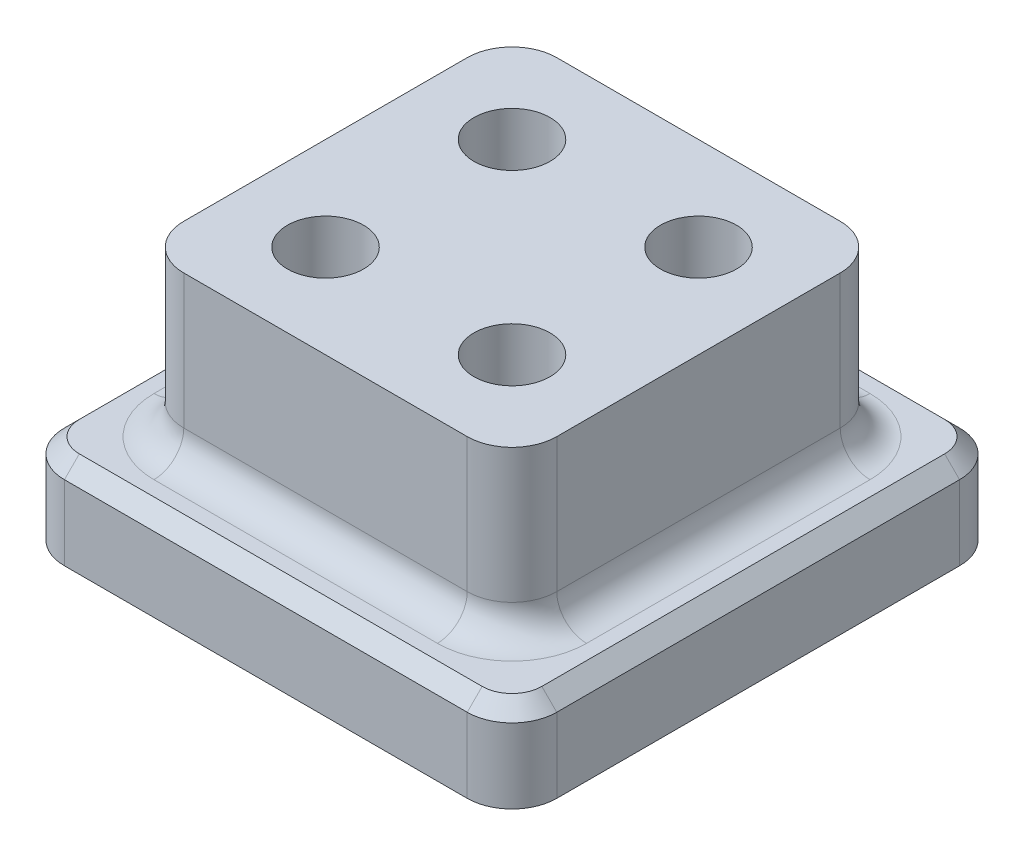
SolidWorks part; units mm, degrees
ref_plane "前视基准面" through (0, 0, 0) normal (0, 0, 1) x (1, 0, 0)
ref_plane "上视基准面" through (0, 0, 0) normal (0, 1, 0) x (1, 0, 0)
ref_plane "右视基准面" through (0, 0, 0) normal (1, 0, 0) x (0, 0, -1)
sketch "草图1" plane through (0, 0, 0) normal (0, 1, 0) x (1, 0, 0)
  line L1 (-10.5, 10.5) -> (10.5, 10.5) construction
  line L2 (-10.5, 10.5) -> (-10.5, -10.5) construction
  line L3 (-10.5, -10.5) -> (10.5, -10.5) construction
  line L4 (10.5, 10.5) -> (10.5, -10.5) construction
  line L5 (-10.5, 10.5) -> (10.5, -10.5) construction
  line L6 (-10.5, -10.5) -> (10.5, 10.5) construction
  line L7 (-13.5, 16.5) -> (13.5, 16.5)
  line L8 (-16.5, 13.5) -> (-16.5, -13.5)
  line L9 (-13.5, -16.5) -> (13.5, -16.5)
  line L10 (16.5, 13.5) -> (16.5, -13.5)
  line L11 (-16.5, 16.5) -> (21.0757, -21.0757) construction
  line L12 (-16.5, -16.5) -> (16.5, 16.5) construction
  circle A0 centre (-10.5, 10.5) radius 2.175
  circle A1 centre (10.5, 10.5) radius 2.175
  circle A2 centre (10.5, -10.5) radius 2.175
  circle A3 centre (-10.5, -10.5) radius 2.175
  circle A4 centre (0, 0) radius 2.175
  arc A5 (-16.5, -13.5) -> (-13.5, -16.5) centre (-13.5, -13.5) ccw
  arc A6 (13.5, -16.5) -> (16.5, -13.5) centre (13.5, -13.5) ccw
  arc A7 (13.5, 16.5) -> (16.5, 13.5) centre (13.5, 13.5) cw
  arc A8 (-13.5, 16.5) -> (-16.5, 13.5) centre (-13.5, 13.5) ccw
  point P0 (0, 0)
  point P6 (0, 0)
  dimension "D1" = 4.35
  dimension "D4" = 3
  dimension "D2" = 21
  dimension "D3" = 6
  dimension "D5" = 33
  dimension "D6" = 33
extrude "凸台-拉伸4" add sketch "草图1" along normal blind 6 contours A3 | A4 | A0 | A1 | A2 | L7 A8 L8 A5 L9 A6 L10 A7 A0 A1 A2 A3 A4 region at (0, 0, -16.0333) region at (-10.5, 0, -10.5) region at (10.5, 0, -10.5) region at (10.5, 0, 10.5) region at (-10.5, 0, 10.5) region at (0, 0, 0)
extrude "切除-拉伸3" cut sketch "草图1<3>" along normal blind 4.5 contours A2 | A1 | A0 | A3 | A4 region at (-10.5, 0, -10.5) region at (10.5, 0, -10.5) region at (10.5, 0, 10.5) region at (-10.5, 0, 10.5) region at (0, 0, 0)
sketch "草图1<3>" plane through (0, 0, 0) normal (0, 1, 0) x (1, 0, 0) same geometry as "草图1"
sketch "草图8" plane through (0, 6, 0) normal (0, 1, 0) x (1, 0, 0)
  line L1 (-9.5, 12.5) -> (9.5, 12.5)
  line L2 (-12.5, 9.5) -> (-12.5, -9.5)
  line L3 (-9.5, -12.5) -> (9.5, -12.5)
  line L4 (12.5, 9.5) -> (12.5, -9.5)
  line L5 (-12.5, 12.5) -> (12.5, -12.5) construction
  line L6 (-12.5, -12.5) -> (12.5, 12.5) construction
  arc A0 (9.5, -12.5) -> (12.5, -9.5) centre (9.5, -9.5) ccw
  arc A1 (-12.5, -9.5) -> (-9.5, -12.5) centre (-9.5, -9.5) ccw
  arc A2 (9.5, 12.5) -> (12.5, 9.5) centre (9.5, 9.5) cw
  arc A3 (-9.5, 12.5) -> (-12.5, 9.5) centre (-9.5, 9.5) ccw
  circle A4 centre (0, 0) radius 8.8388 construction
  circle A5 centre (-6.25, 6.25) radius 2.55
  circle A6 centre (6.25, 6.25) radius 2.55
  circle A7 centre (-6.25, -6.25) radius 2.55
  circle A8 centre (6.25, -6.25) radius 2.55
  point P1 (0, 0)
  dimension "D1" = 3
  dimension "D2" = 5.1
  dimension "D3" = 12.5
  dimension "D4" = 25
extrude "凸台-拉伸5" add sketch "草图8" along normal blind 11
fillet "圆角1" radius 2 8 edges at (-11.6213, 6, 11.6213) (-12.5, 6, 0) (-11.6213, 6, -11.6213) (0, 6, -12.5) (11.6213, 6, -11.6213) (12.5, 6, 0) (11.6213, 6, 11.6213) (0, 6, 12.5)
extrude "切除-拉伸4" cut sketch "草图8<2>" against normal offset from surface (5 mm away) 1 contours A5 | A6 | A8 | A7 region at (-6.25, 6, -6.25) region at (6.25, 6, -6.25) region at (-6.25, 6, 6.25) region at (6.25, 6, 6.25) up to face at (0, 0, 2.175)
sketch "草图8<2>" plane through (0, 6, 0) normal (0, 1, 0) x (1, 0, 0) same geometry as "草图8"
chamfer "倒角1" distance 1 angle 45 8 edges at (-16.5, 6, 0) (-15.6213, 6, -15.6213) (-15.6213, 6, 15.6213) (0, 6, -16.5) (0, 6, 16.5) (15.6213, 6, -15.6213) (15.6213, 6, 15.6213) (16.5, 6, 0)
